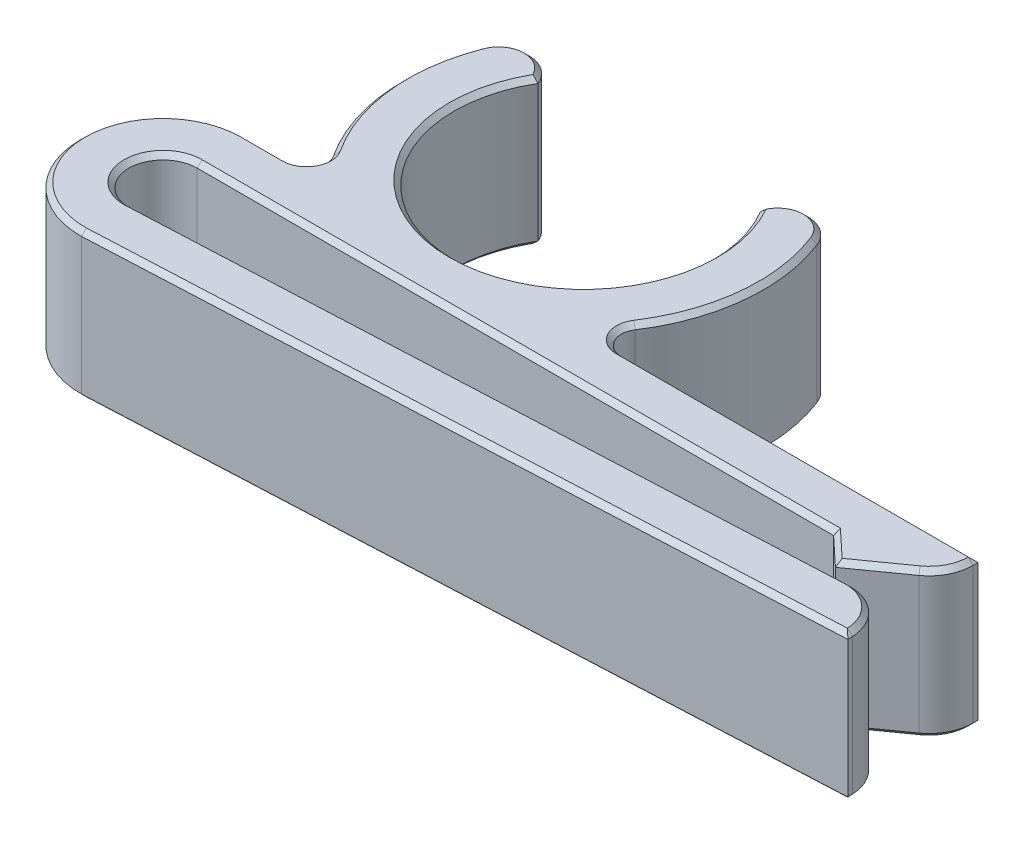
SolidWorks part; units mm, degrees
ref_plane "Front Plane" through (0, 0, 0) normal (0, 0, 1) x (1, 0, 0)
ref_plane "Top Plane" through (0, 0, 0) normal (0, 1, 0) x (1, 0, 0)
ref_plane "Right Plane" through (0, 0, 0) normal (1, 0, 0) x (0, 0, -1)
sketch "Sketch1" plane through (0, 0, 0) normal (0, 1, 0) x (1, 0, 0)
  line L0 (-21.3603, -18.25) -> (43.909, -18.25)
  line L1 (-21.3603, -25.25) -> (49.1446, -21.9598)
  line L2 (-21.2182, -30.2488) -> (53.8728, -26.7446)
  line L3 (-21.3603, -13.25) -> (-12.9108, -13.25)
  line L4 (53.7213, -13.25) -> (53.7213, -13.75)
  line L5 (53.8495, -26.2451) -> (53.8728, -26.7446)
  line L6 (-21.3603, -18.25) -> (53.7213, -18.25) construction
  line L7 (-21.3603, -25.25) -> (53.6397, -21.75) construction
  line L8 (43.909, -18.25) -> (46.8305, -20.9802)
  line L9 (46.8305, -20.9802) -> (51.8332, -17.4144)
  line L10 (-21.3603, -3.4243) -> (-21.3603, -44.2326) construction
  line L11 (-24.5505, 6.75) -> (34.718, 6.75) construction
  line L12 (12.9108, -13.25) -> (53.7213, -13.25)
  line L13 (-21.3603, -13.25) -> (53.7213, -13.25) construction
  arc A0 (-11.4018, 6.75) -> (11.4018, 6.75) centre (0, 0) ccw
  arc A1 (12.9108, -13.25) -> (17.2246, 6.75) centre (0, 0) ccw
  arc A2 (-21.3603, -18.25) -> (-21.3603, -25.25) centre (-21.3603, -21.75) ccw
  arc A3 (-21.3603, -13.25) -> (-21.2182, -30.2488) centre (-21.3603, -21.75) ccw
  arc A4 (51.8332, -17.4144) -> (53.7213, -13.75) centre (49.2213, -13.75) ccw
  arc A5 (49.1446, -21.9598) -> (53.8495, -26.2451) centre (49.3544, -26.4549) cw
  arc A6 (-17.2246, 6.75) -> (-12.9108, -13.25) centre (0, 0) ccw
  arc A7 (-17.2246, 6.75) -> (-11.4018, 6.75) centre (-14.3132, 5.6091) cw
  arc A8 (17.2246, 6.75) -> (11.4018, 6.75) centre (14.3132, 5.6091) ccw
  point P7 (0, 0)
  point P17 (53.7213, -18.25)
  point P21 (53.6397, -21.75)
  point P32 (14.0008, 4.2251)
  point P33 (0, 0)
  dimension "D1" = 26.5
  dimension "D2" = 37
  dimension "D3" = 7
  dimension "D7" = 4.5
  dimension "D4" = 75
  dimension "D5" = 3.5
  dimension "D8" = 20
  dimension "D6" = 5
extrude "Boss-Extrude1" add sketch "Sketch1" along normal blind 15
fillet "Fillet1" radius 2 2 edges at (-12.9108, 7.5, 13.25) (12.9108, 7.5, 13.25)
chamfer "Chamfer1" distance 0.5 angle 45 40 edges at (0, 0, 13.25) (0, 15, 13.25) (11.2743, 0, 18.25) (45.3697, 0, 19.6151) (49.3319, 0, 19.1973) (53.2216, 0, 15.8111) (53.7213, 0, 13.5) (35.4293, 0, 13.25) (15.3773, 0, 12.2) (18.4006, 0, 1.9152) (14.3132, 0, -8.7361) (-14.3132, 0, -8.7361) (-18.4006, 0, 1.9152) (-15.3773, 0, 12.2) (-19.2488, 0, 13.25) (-29.86, 0, 21.821) (16.3273, 0, 28.4967) (53.8611, 0, 26.4948) (52.3846, 0, 23.128) (13.8922, 0, 23.6049) (-24.8603, 0, 21.75) (13.8922, 15, 23.6049) (52.3846, 15, 23.128) (53.8611, 15, 26.4948) (16.3273, 15, 28.4967) (-29.86, 15, 21.821) (-19.2488, 15, 13.25) (-15.3773, 15, 12.2) (-18.4006, 15, 1.9152) (-14.3132, 15, -8.7361) (14.3132, 15, -8.7361) (18.4006, 15, 1.9152) (15.3773, 15, 12.2) (35.4293, 15, 13.25) (53.7213, 15, 13.5) (53.2216, 15, 15.8111) (49.3319, 15, 19.1973) (45.3697, 15, 19.6151) (11.2743, 15, 18.25) (-24.8603, 15, 21.75)
